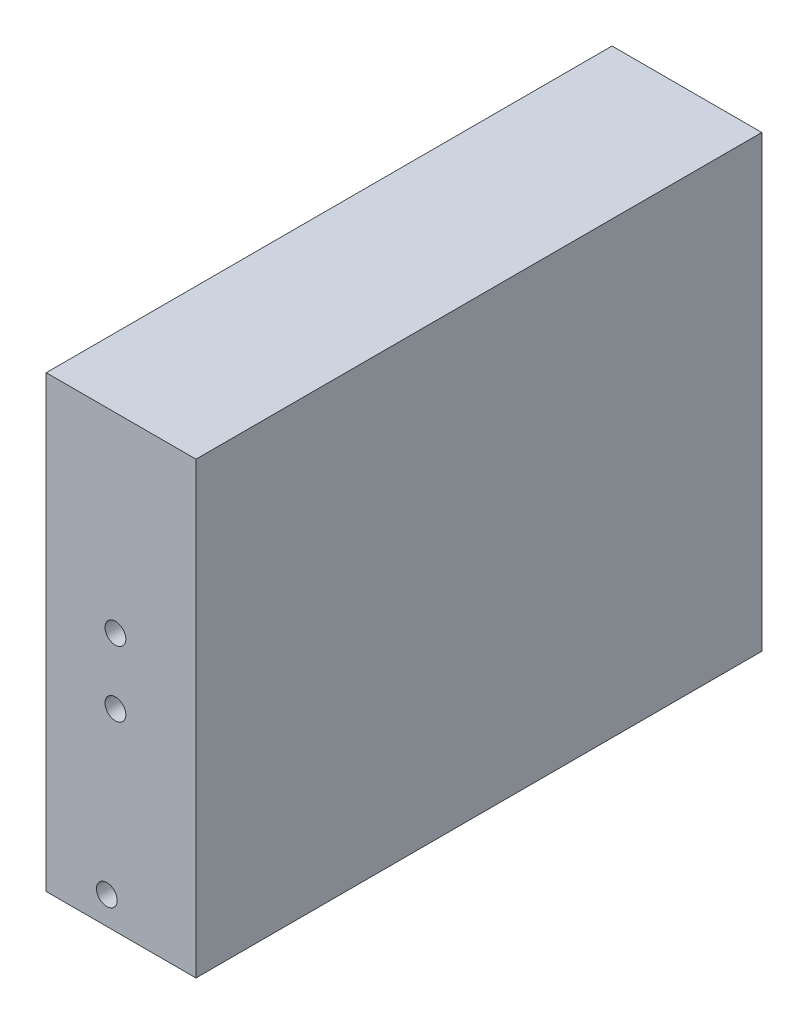
SolidWorks part; units mm, degrees
ref_plane "Front Plane" through (0, 0, 0) normal (0, 0, 1) x (1, 0, 0)
ref_plane "Top Plane" through (0, 0, 0) normal (0, 1, 0) x (1, 0, 0)
ref_plane "Right Plane" through (0, 0, 0) normal (1, 0, 0) x (0, 0, -1)
sketch "Sketch1" plane through (0, 0, 0) normal (0, 0, 1) x (1, 0, 0)
  line L1 (0, 0) -> (57.15, 0)
  line L2 (0, 0) -> (0, 171.45)
  line L3 (0, 171.45) -> (57.15, 171.45)
  line L4 (57.15, 0) -> (57.15, 171.45)
  dimension "D1" = 57.15
  dimension "D2" = 171.45
extrude "Boss-Extrude1" add sketch "Sketch1" along normal blind 215.9
sketch "Sketch2" plane through (0, 0, 0) normal (0, 0, -1) x (-1, 0, 0)
  circle A0 centre (-24.41, 70.569) radius 3.175 construction
  circle A1 centre (-24.41, 70.569) radius 3.175
extrude "Cut-Extrude1" cut sketch "Sketch2" against normal blind 46.74 contours A1
sketch "Sketch3" plane through (0, 0, 0) normal (0, 0, -1) x (-1, 0, 0)
  circle A0 centre (-24.41, 70.569) radius 3.9687 construction
  circle A1 centre (-24.41, 70.569) radius 3.9687
extrude "Cut-Extrude2" cut sketch "Sketch3" against normal blind 13.04 contours A1
sketch "Sketch4" plane through (0, 0, 215.9) normal (0, 0, 1) x (1, 0, 0)
  circle A1 centre (26.41, 73.569) radius 3.175 construction
  circle A2 centre (26.41, 98.569) radius 3.175 construction
  circle A4 centre (26.41, 73.569) radius 3.175
  circle A5 centre (26.41, 98.569) radius 3.175
extrude "Cut-Extrude3" cut sketch "Sketch4" against normal blind 35.16 contours A5 | A4
sketch "Sketch5" plane through (0, 0, 215.9) normal (0, 0, 1) x (1, 0, 0)
  circle A0 centre (23.13, 10.569) radius 3.175 construction
  circle A1 centre (23.13, 10.569) radius 3.175
extrude "Cut-Extrude4" cut sketch "Sketch5" against normal blind 94.66 contours A1
sketch "Sketch6" plane through (0, 0, 215.9) normal (0, 0, 1) x (1, 0, 0)
  circle A0 centre (26.41, 73.569) radius 3.9687 construction
  circle A1 centre (26.41, 98.569) radius 3.9687 construction
  circle A2 centre (26.41, 73.569) radius 3.9687
  circle A3 centre (26.41, 98.569) radius 3.9687
extrude "Cut-Extrude5" cut sketch "Sketch6" against normal blind 10.16 contours A3 | A2
sketch "Sketch7" plane through (0, 0, 215.9) normal (0, 0, 1) x (1, 0, 0)
  circle A0 centre (23.13, 10.569) radius 3.9687 construction
  circle A1 centre (23.13, 10.569) radius 3.9687
extrude "Cut-Extrude6" cut sketch "Sketch7" against normal blind 69.66 contours A1
sketch "Sketch8" plane through (0, 0, 0) normal (0, 0, -1) x (-1, 0, 0)
  point P0 (-57.15, 171.45)
